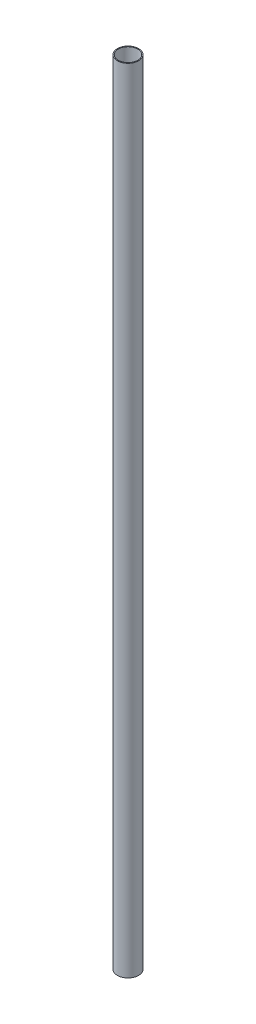
SolidWorks part; units mm, degrees
material "Thornel Mat VMA"
ref_plane "前视基准面" through (0, 0, 0) normal (0, 0, 1) x (1, 0, 0)
ref_plane "上视基准面" through (0, 0, 0) normal (0, 1, 0) x (1, 0, 0)
ref_plane "右视基准面" through (0, 0, 0) normal (1, 0, 0) x (0, 0, -1)
sketch "草图1" plane through (0, 0, 0) normal (0, 1, 0) x (1, 0, 0)
  circle A0 centre (0, 0) radius 5.5
  circle A1 centre (0, 0) radius 6
  dimension "D1" = 12
  dimension "D2" = 0.5
extrude "凸台-拉伸1" add sketch "草图1" along normal blind 447.5
